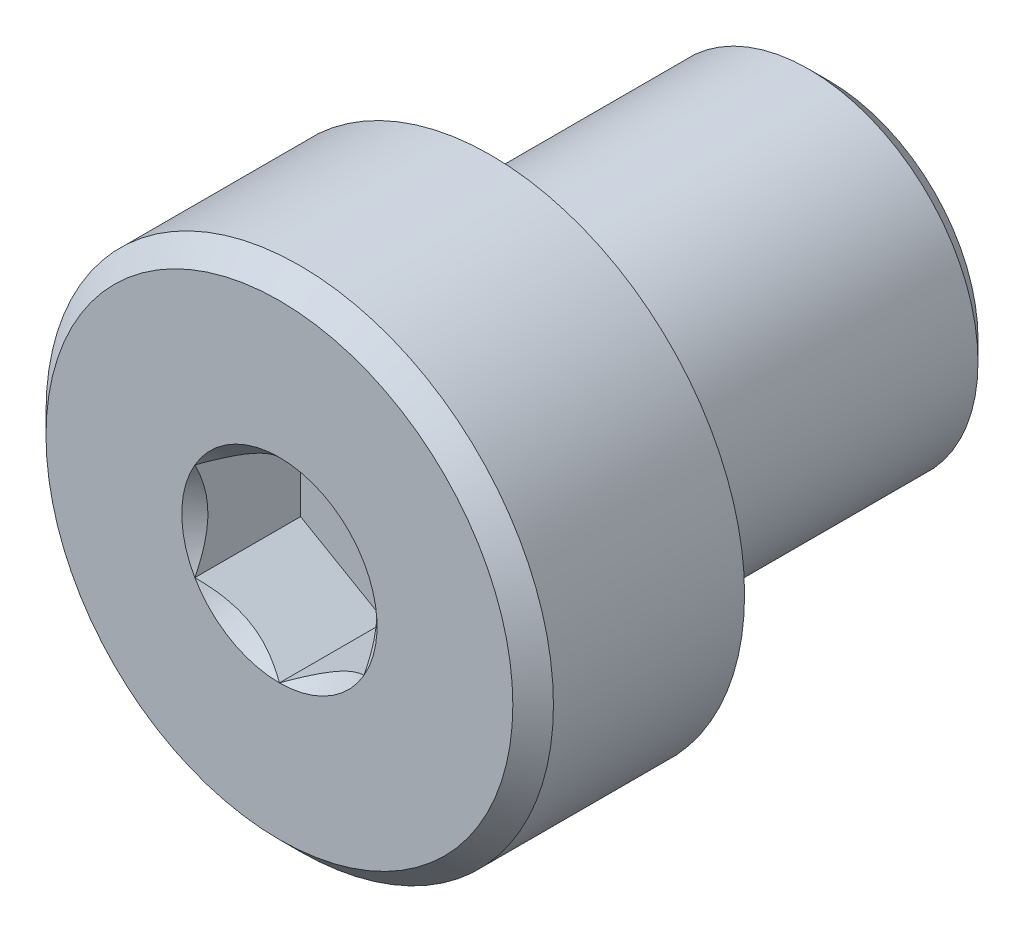
SolidWorks part; units mm, degrees
material "Plain Carbon Steel"
ref_plane "Front" through (0, 0, 0) normal (0, 0, 1) x (1, 0, 0)
ref_plane "Top" through (0, 0, 0) normal (0, 1, 0) x (1, 0, 0)
ref_plane "Right" through (0, 0, 0) normal (1, 0, 0) x (0, 0, -1)
sketch "Sketch1" plane through (0, 0, 0) normal (1, 0, 0) x (0, 0, -1)
  line L0 (0, 9.525) -> (7.9375, 9.525)
  line L1 (7.9375, 9.525) -> (7.9375, 6.35)
  line L2 (7.9375, 6.35) -> (20.6375, 6.35)
  line L3 (20.6375, 6.35) -> (20.6375, 2.413)
  line L4 (20.6375, 2.413) -> (14.2875, 2.413)
  line L5 (14.2875, 2.413) -> (14.2875, 0)
  line L6 (14.2875, 0) -> (0, 0)
  line L7 (0, 0) -> (0, 9.525)
  line L8 (0, 9.525) -> (0, -9.525) construction
  line L9 (14.2875, 2.413) -> (14.2875, -2.413) construction
  line L10 (20.6375, 6.35) -> (20.6375, -6.35) construction
  point P12 (20.6375, 0)
revolve "Revolve1" add sketch "Sketch1" angle 360 mid plane about L6
sketch "Sketch14" plane through (0, 0, 0) normal (1, 0, 0) x (0, 0, -1)
  line L0 (14.2875, -2.413) -> (20.6375, -2.413) construction
  line L1 (20.6375, 2.413) -> (14.2875, 2.413) construction
  line L2 (14.2875, -2.413) -> (14.2875, 2.413) construction
  line L3 (14.2875, -2.413) -> (20.6375, -2.413)
  line L4 (20.6375, 2.413) -> (14.2875, 2.413)
  line L5 (14.2875, -2.413) -> (14.2875, 2.413)
ref_plane "Plane1" through (0, 0, -14.2875) normal (0, 0, 1) x (1, 0, 0)
sketch "Sketch3" plane through (0, 0, -20.6375) normal (0, 0, 1) x (1, 0, 0)
  circle A0 centre (0, 0) radius 2.413
curve "Helix/Spiral1" pitch 0.7937 height 7.1437 radius 2.413 centre (0, 0, -20.6375) axis (0, 0, 1) start towards (0, 1, 0)
sketch "Sketch4" plane through (0, 0, 0) normal (1, 0, 0) x (0, 0, -1)
  line L0 (20.6375, 2.413) -> (21.332, 2.413)
  line L1 (21.332, 2.413) -> (21.0344, 1.8974)
  line L3 (21.0344, 1.8974) -> (20.9352, 1.8974)
  line L4 (20.9352, 1.8974) -> (20.6375, 2.413)
  line L5 (20.7863, 2.1552) -> (21.1832, 2.1552) construction
  dimension "D1" = 60
  dimension "D2" = 0.0992
  dimension "D3" = 0.3969
sweep "Sweep1" add profiles "Sketch4" path "Helix/Spiral1"
sketch "Sketch10" plane through (0, 0, -20.6375) normal (0, 0, -1) x (-1, 0, 0)
  circle A0 centre (0, 0) radius 2.606
  dimension "D1" = 5.2121
extrude "Cut-Extrude5" cut sketch "Sketch10" against normal blind 2.54 draft 45 and the other way through all
chamfer "Chamfer2" distance 0.762 angle 45 2 edges at (0, 9.525, 0) (0, 6.35, -20.6375)
sketch "Sketch8" plane through (0, 0, 0) normal (0, 0, 1) x (1, 0, 0)
  line L1 (3.175, 1.8331) -> (0, 3.6662)
  line L2 (0, 3.6662) -> (-3.175, 1.8331)
  line L3 (-3.175, 1.8331) -> (-3.175, -1.8331)
  line L4 (-3.175, -1.8331) -> (0, -3.6662)
  line L5 (0, -3.6662) -> (3.175, -1.8331)
  line L6 (3.175, -1.8331) -> (3.175, 1.8331)
  circle A0 centre (0, 0) radius 3.175 construction
  dimension "Hex" = 6.35
extrude "Cut-Extrude3" cut sketch "Sketch8" against normal blind 3.9688
sketch "Sketch9" plane through (0, 0, 0) normal (0, 0, 1) x (1, 0, 0)
  circle A0 centre (0, 0) radius 3.6662
extrude "Cut-Extrude4" cut sketch "Sketch9" against normal blind 3.9688 draft 45
sketch "reference 1" plane through (0, 0, -7.9375) normal (0, 0, -1) x (-1, 0, 0)
  circle A1 centre (0, 0) radius 9.525
  circle A2 centre (0, 0) radius 9.525 construction
sketch "Sketch11" plane through (0, 0, -14.2875) normal (0, 0, -1) x (-1, 0, 0)
  circle A1 centre (0, 0) radius 2.606 construction
  circle A2 centre (0, 0) radius 1.336
  circle A3 centre (0, 0) radius 1.336
  circle A4 centre (0, 0) radius 2.606
  dimension "D1" = 1.27
sketch "Sketch12" plane through (0, 0, -14.2875) normal (0, 0, -1) x (-1, 0, 0)
  circle A0 centre (0, 0) radius 5.588 construction
  circle A1 centre (0, 0) radius 5.588
extrude "Boss-Extrude2" add sketch "Sketch12" against normal blind 0.635
equation "\"D3@Helix/Spiral1\" = \"Thread Lg@Sketch1\" + \"D4@Helix/Spiral1\""
equation "\"D1@Cut-Extrude3\" = \"Head Ht@Sketch1\" * .5"
equation "\"D1@Cut-Extrude4\" = \"D1@Cut-Extrude3\""
equation "\"D1@Chamfer2\" = \"Head Dia@Sketch1\" * .04"
equation "\"D2@Sketch4\" = \"D4@Helix/Spiral1\" * .125"
equation "\"D3@Sketch4\" = \"D4@Helix/Spiral1\" * .5"
equation "\"D1@Sketch10\" = \"Thread Dia@Sketch1\" * 1.08"
